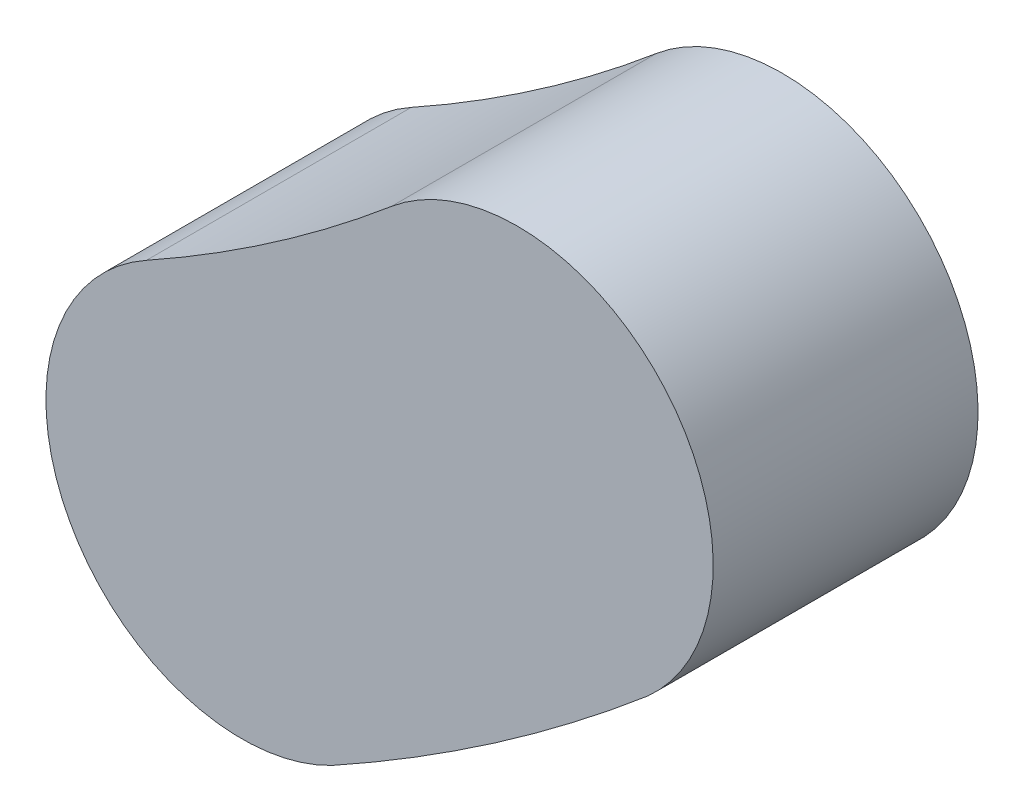
SolidWorks part; units mm, degrees
material "ABS PC"
ref_plane "Front Plane" through (0, 0, 0) normal (0, 0, 1) x (1, 0, 0)
ref_plane "Top Plane" through (0, 0, 0) normal (0, 1, 0) x (1, 0, 0)
ref_plane "Right Plane" through (0, 0, 0) normal (1, 0, 0) x (0, 0, -1)
sketch "Sketch2" plane through (0, 0, 0) normal (0, 0, 1) x (1, 0, 0)
  line L0 (0, 90.8261) -> (25.6962, 44.7008) construction
  line L3 (0, 90.8261) -> (34.0252, 50.4513) construction
  arc A0 (22.8187, 49.8661) -> (28.4232, 39.4544) centre (25.6962, 44.7008) ccw
  arc A5 (28.4232, 39.4544) -> (37.9647, 46.0421) centre (0, 90.8261) ccw
  arc A7 (20.3779, 42.117) -> (36.7588, 52.9232) centre (0, 90.8261) ccw construction
  arc A9 (22.8187, 49.8661) -> (30.215, 54.9726) centre (0, 90.8261) ccw
  arc A10 (30.215, 54.9726) -> (37.7031, 45.8217) centre (34.0252, 50.4513) cw
  point P10 (0, 0)
  dimension "D1" = 52.8
  dimension "D5" = 11
extrude "Boss-Extrude1" add sketch "Sketch2" along normal blind 8 contours A10 A9 A0 A5 region at (29.9084, 47.507, 0)
